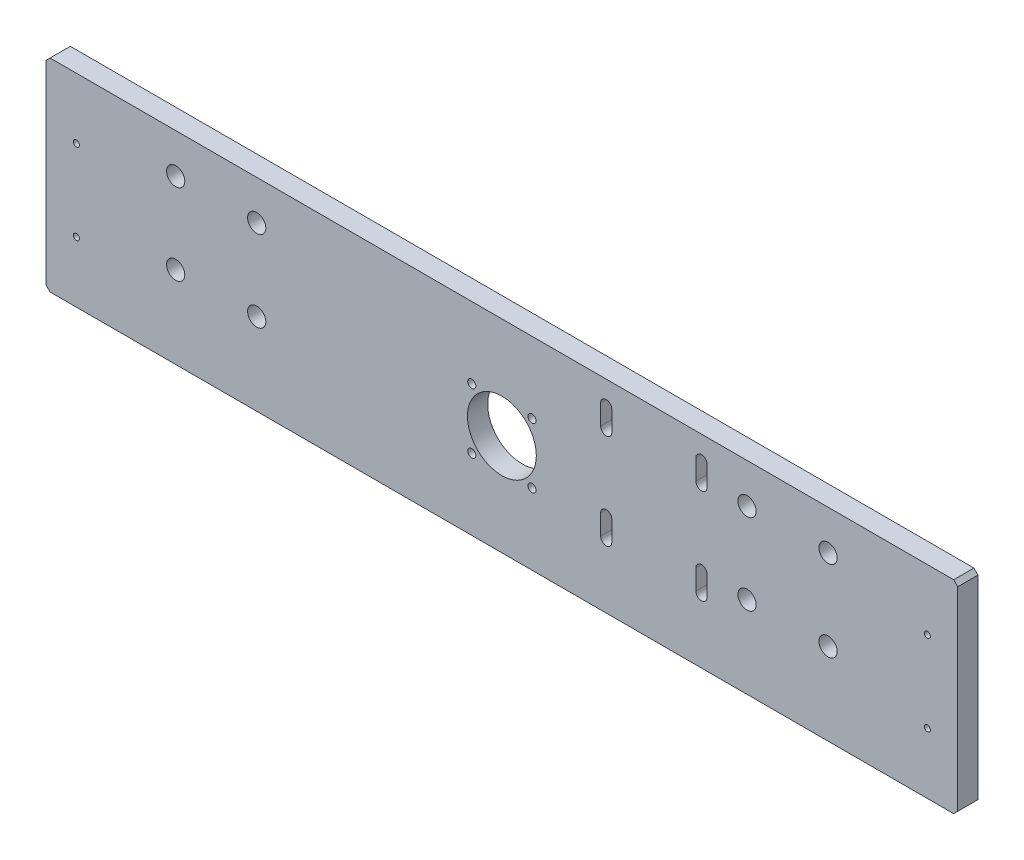
SolidWorks part; units mm, degrees
ref_plane "Piano frontale" through (0, 0, 0) normal (0, 0, 1) x (1, 0, 0)
ref_plane "Piano superiore" through (0, 0, 0) normal (0, 1, 0) x (1, 0, 0)
ref_plane "Piano destro" through (0, 0, 0) normal (1, 0, 0) x (0, 0, -1)
sketch "Schizzo1" plane through (0, 0, 0) normal (0, 0, 1) x (1, 0, 0)
  line L0 (225, 100) -> (225, 0) construction
  line L1 (2, 0) -> (448, 0)
  line L2 (0, 2) -> (0, 98)
  line L3 (2, 100) -> (448, 100)
  line L4 (450, 2) -> (450, 98)
  line L5 (84, 80.5) -> (84, 40.5) construction
  line L7 (225, 50) -> (243.5099, 50) construction
  line L9 (225, 50) -> (205.51, 69.49) construction
  line L21 (0, 98) -> (2, 100)
  line L22 (2, 0) -> (0, 2)
  line L23 (448, 0) -> (450, 2)
  line L24 (448, 100) -> (450, 98)
  line L25 (225, 50) -> (450, 50) construction
  line L26 (316.3685, 60) -> (282.8483, 60) construction
  line L27 (323.5, 88.5) -> (323.5, 78.5) construction
  line L28 (320.75, 88.5) -> (320.75, 78.5)
  line L29 (326.25, 88.5) -> (326.25, 78.5)
  line L30 (276.5, 88.5) -> (276.5, 78.5) construction
  line L31 (279.25, 88.5) -> (279.25, 78.5)
  line L32 (273.75, 88.5) -> (273.75, 78.5)
  line L33 (323.5, 31.5) -> (323.5, 41.5) construction
  line L34 (320.75, 31.5) -> (320.75, 41.5)
  line L35 (326.25, 31.5) -> (326.25, 41.5)
  line L36 (276.5, 31.5) -> (276.5, 41.5) construction
  line L37 (279.25, 31.5) -> (279.25, 41.5)
  line L38 (273.75, 31.5) -> (273.75, 41.5)
  line L42 (300, 100) -> (300, 0) construction
  circle A0 centre (225, 50) radius 17
  circle A1 centre (225, 50) radius 21 construction
  circle A2 centre (239.8492, 64.8492) radius 2
  circle A3 centre (239.8492, 35.1508) radius 2
  circle A4 centre (210.1508, 35.1508) radius 2
  circle A11 centre (15, 30) radius 1.5
  circle A12 centre (435, 30) radius 1.5
  circle A13 centre (210.1508, 64.8492) radius 2
  circle A17 centre (435, 70) radius 1.5
  circle A18 centre (15, 70) radius 1.5
  arc A19 (320.75, 88.5) -> (326.25, 88.5) centre (323.5, 88.5) cw
  arc A20 (326.25, 78.5) -> (320.75, 78.5) centre (323.5, 78.5) cw
  arc A21 (279.25, 88.5) -> (273.75, 88.5) centre (276.5, 88.5) ccw
  arc A22 (273.75, 78.5) -> (279.25, 78.5) centre (276.5, 78.5) ccw
  arc A23 (320.75, 31.5) -> (326.25, 31.5) centre (323.5, 31.5) ccw
  arc A24 (326.25, 41.5) -> (320.75, 41.5) centre (323.5, 41.5) ccw
  arc A25 (279.25, 31.5) -> (273.75, 31.5) centre (276.5, 31.5) cw
  arc A26 (273.75, 41.5) -> (279.25, 41.5) centre (276.5, 41.5) cw
  circle A29 centre (104, 80.5) radius 4.5
  circle A30 centre (104, 40.5) radius 4.5
  circle A32 centre (64, 80.5) radius 4.5
  circle A33 centre (64, 40.5) radius 4.5
  circle A34 centre (386, 40.5) radius 4.5
  circle A35 centre (346, 40.5) radius 4.5
  circle A36 centre (346, 80.5) radius 4.5
  circle A37 centre (386, 80.5) radius 4.5
  point P0 (0, 0)
  point P1 (450, 100)
  point P2 (0, 100)
  point P3 (450, 0)
  point P9 (210.1508, 64.8492)
  point P13 (210.1508, 64.8492)
  point P80 (300, 60)
  point P83 (323.5, 83.5)
  point P90 (276.5, 83.5)
  point P97 (323.5, 36.5)
  point P104 (276.5, 36.5)
  dimension "D4" = 34
  dimension "D10" = 20
  dimension "D15" = 3
  dimension "D17" = 4
  dimension "D8" = 45
  dimension "D5" = 42
  dimension "D1" = 100
  dimension "D2" = 450
  dimension "D3" = 50
  dimension "D6" = 19.5
  dimension "D7" = 40
  dimension "D14" = 30
  dimension "D16" = 15
  dimension "D18" = 40
  dimension "D23" = 23.5
  dimension "D24" = 23.5
  dimension "D26" = 5.5
  dimension "D27" = 10
  dimension "D29" = 150
extrude "Boss-Extrude1" add sketch "Schizzo1" against normal blind 10
